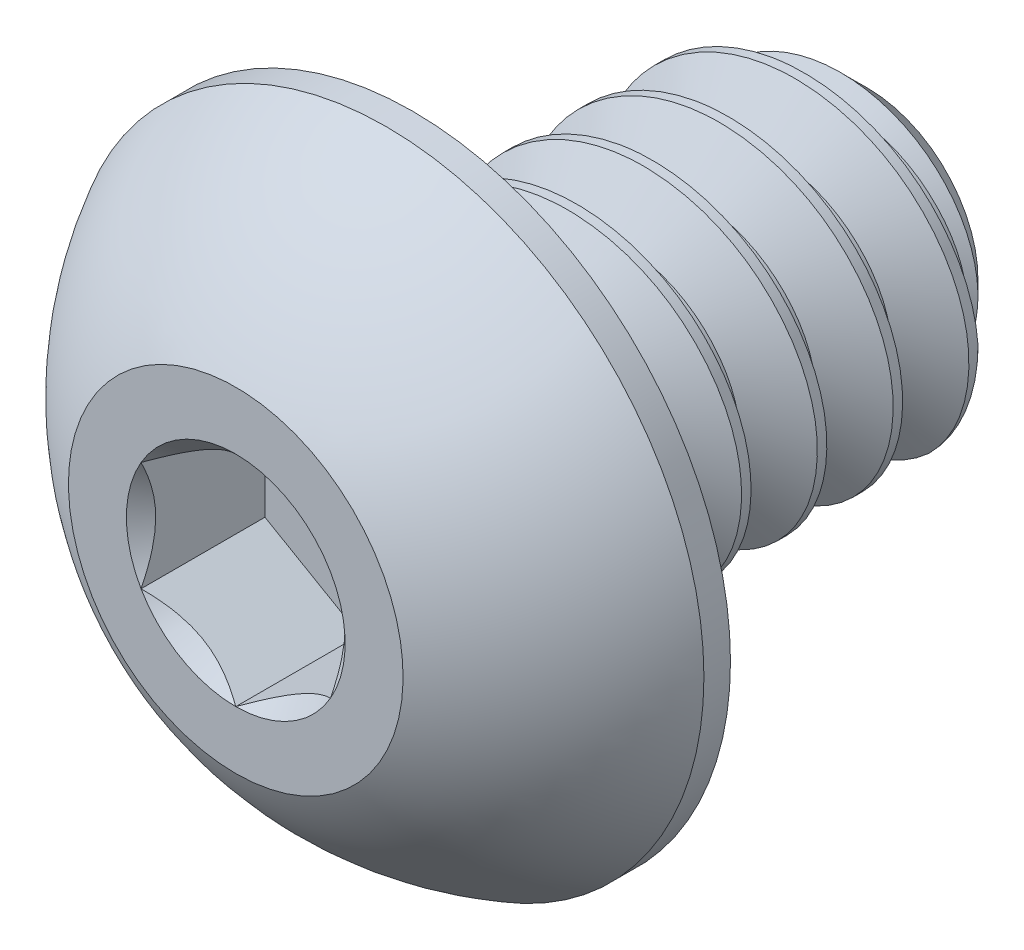
SolidWorks part; units mm, degrees
ref_plane "Front" through (0, 0, 0) normal (0, 0, 1) x (1, 0, 0)
ref_plane "Top" through (0, 0, 0) normal (0, 1, 0) x (1, 0, 0)
ref_plane "Right" through (0, 0, 0) normal (1, 0, 0) x (0, 0, -1)
sketch "Sketch1" plane through (0, 0, 0) normal (1, 0, 0) x (0, 0, -1)
  line L2 (1.8542, 1.7526) -> (6.6167, 1.7526)
  line L3 (6.6167, 1.7526) -> (6.6167, 0)
  line L4 (6.6167, 0) -> (1.8542, 0)
  line L6 (1.5761, 3.3274) -> (1.8542, 3.3274) construction
  line L7 (6.6167, 1.7526) -> (6.6167, -1.7526) construction
  line L8 (0, 0) -> (1.8542, 0) construction
  line L9 (1.8542, 3.3274) -> (1.8542, -3.3274) construction
  line L11 (1.8542, 1.7526) -> (1.8542, 0)
  line L13 (0, 0.9922) -> (0, -0.9922) construction
  line L14 (0, 0.9922) -> (0, 1.7526) construction
  arc A3 (0, 1.7526) -> (1.5761, 3.3274) centre (3.326, 0) cw construction
  dimension "D1" = 0.2781
  dimension "Head Ht" = 1.8542
  dimension "Head Dia" = 6.6548
  dimension "Dia" = 3.5052
  dimension "Lg" = 4.7625
  dimension "Hex" = 1.9844
revolve "Revolve1" add sketch "Sketch1" angle 360 about L4
sketch "Sketch3" plane through (0, 0, -6.6167) normal (0, 0, -1) x (-1, 0, 0)
  circle A0 centre (0, 0) radius 1.7526
curve "Helix/Spiral1" pitch 0.7937 height 6.6167 radius 1.7526 centre (0, 0, -6.6167) axis (0, 0, 1) start towards (0, 1, 0)
sketch "Sketch2" plane through (0, 0, 0) normal (1, 0, 0) x (0, 0, -1)
  line L0 (6.6167, 1.7526) -> (7.3112, 1.7526)
  line L1 (7.3112, 1.7526) -> (7.0136, 1.237)
  line L2 (7.0136, 1.237) -> (6.9144, 1.237)
  line L3 (6.9144, 1.237) -> (6.6167, 1.7526)
  line L4 (6.7655, 1.4948) -> (7.1624, 1.4948) construction
  dimension "D1" = 60
  dimension "D2" = 0.0992
  dimension "D3" = 0.3969
chamfer "Chamfer1" distance 0.5953 angle 45 1 edges at (0, 1.7526, -6.6167)
sweep "Cut-Sweep1" cut profiles "Sketch2" path "Helix/Spiral1"
sketch "Sketch7" plane through (0, 0, 0) normal (1, 0, 0) x (0, 0, -1)
  line L6 (1.5761, 3.3274) -> (1.8542, 3.3274) construction
  line L8 (0, 0) -> (1.8542, 0) construction
  line L11 (1.8542, 3.3274) -> (1.8542, -3.3274) construction
  line L12 (1.5761, 3.3274) -> (1.8542, 3.3274)
  line L13 (0, 0) -> (1.8542, 0)
  line L14 (0, 0.9922) -> (0, -0.9922) construction
  line L15 (1.8542, 3.3274) -> (1.8542, 0)
  line L16 (0, 1.7526) -> (0, 0)
  arc A2 (1.5761, 3.3274) -> (0, 1.7526) centre (3.326, 0) ccw construction
  arc A3 (1.5761, 3.3274) -> (0, 1.7526) centre (3.326, 0) ccw
revolve "Revolve2" add sketch "Sketch7" angle 360 about L13
sketch "Sketch5" plane through (0, 0, 0) normal (0, 0, 1) x (1, 0, 0)
  line L1 (0.9922, -0.5728) -> (0.9922, 0.5728)
  line L2 (0.9922, 0.5728) -> (0, 1.1457)
  line L3 (0, 1.1457) -> (-0.9922, 0.5728)
  line L4 (-0.9922, 0.5728) -> (-0.9922, -0.5728)
  line L5 (-0.9922, -0.5728) -> (0, -1.1457)
  line L6 (0, -1.1457) -> (0.9922, -0.5728)
  circle A0 centre (0, 0) radius 0.9922 construction
extrude "Cut-Extrude2" cut sketch "Sketch5" against normal blind 1.2979
sketch "Sketch6" plane through (0, 0, 0) normal (0, 0, 1) x (1, 0, 0)
  circle A0 centre (0, 0) radius 1.1457
extrude "Cut-Extrude3" cut sketch "Sketch6" against normal blind 1.2979 draft 45
sketch "Sketch9" [suppressed] plane through (0, 0, -1.8542) normal (0, 0, 1) x (1, 0, 0)
  circle A2 centre (0, 0) radius 1.7526
extrude "Boss-Extrude2" [suppressed] add sketch "Sketch9" against normal offset from surface (19.05 mm away) 22.225
sketch "Sketch10" plane through (0, 0, 0) normal (1, 0, 0) x (0, 0, -1)
  line L0 (6.6167, 1.7526) -> (6.6167, -1.7526) construction
  point P0 (5.4261, -1.7526)
  dimension "D1" = 1.1906
equation "\"D3@Helix/Spiral1\" = \"Lg@Sketch1\" + \"Head Ht@Sketch1\""
equation "\"D2@Sketch2\" = \"D4@Helix/Spiral1\" * .125"
equation "\"D3@Sketch2\" = \"D4@Helix/Spiral1\" * .5"
equation "\"D1@Chamfer1\" = \"D4@Helix/Spiral1\" * .75"
equation "\"D1@Cut-Extrude2\" = \"Head Ht@Sketch1\" * .7"
equation "\"D1@Sketch1\" = \"Head Ht@Sketch1\" * .15"
equation "\"D1@Sketch10\" = \"D4@Helix/Spiral1\" * 1.5"
equation "\"D1@Cut-Extrude3\" = \"D1@Cut-Extrude2\""
